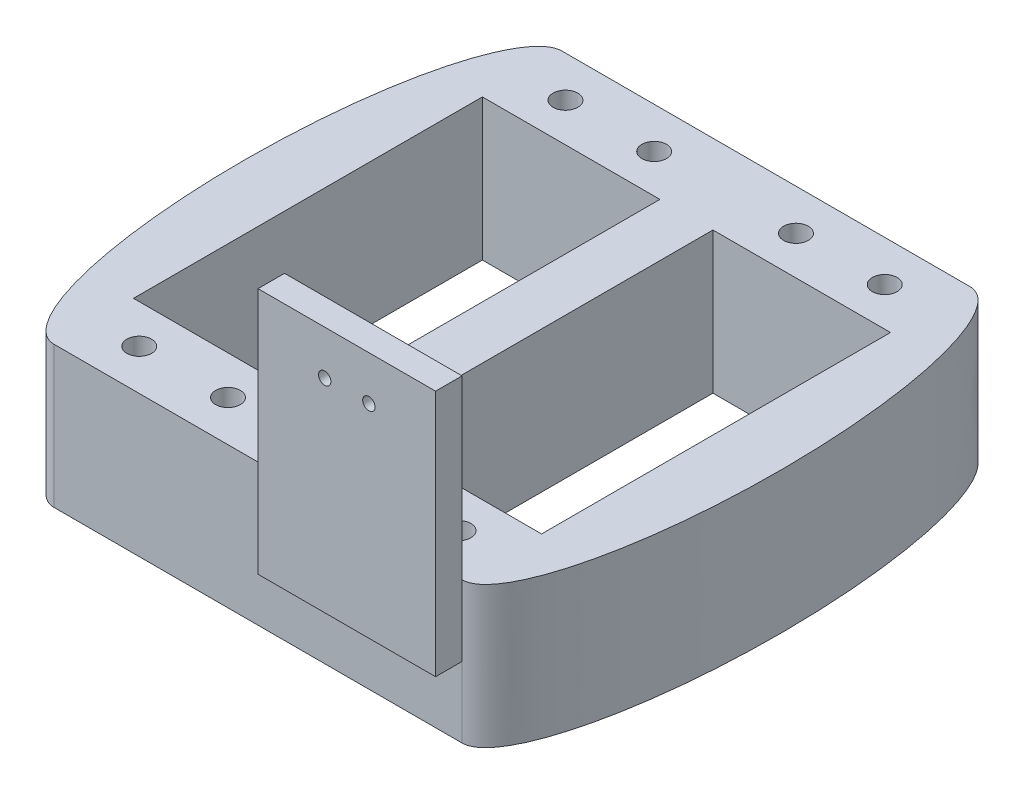
SolidWorks part; units mm, degrees
ref_plane "Front" through (0, 0, 0) normal (0, 0, 1) x (1, 0, 0)
ref_plane "Top" through (0, 0, 0) normal (0, 1, 0) x (1, 0, 0)
ref_plane "Right" through (0, 0, 0) normal (1, 0, 0) x (0, 0, -1)
sketch "Эскиз1" plane through (0, 0, 0) normal (0, 1, 0) x (1, 0, 0)
  line L0 (0, 19.75) -> (0, -19.75) construction
  line L1 (-22.3672, 0) -> (21.2348, 0) construction
  line L2 (0, -19.75) -> (0, -28.75) construction
  line L3 (-10.05, -19.75) -> (10.05, -19.75)
  line L4 (-10.05, -19.75) -> (-10.05, 19.75)
  line L5 (-10.05, 19.75) -> (10.05, 19.75)
  line L6 (10.05, -19.75) -> (10.05, 19.75)
  line L7 (-10.05, -19.75) -> (10.05, 19.75) construction
  line L8 (-10.05, 19.75) -> (10.05, -19.75) construction
  line L9 (10.05, -19.75) -> (-10.05, -19.75)
  line L10 (10.05, -19.75) -> (10.05, -28.75)
  line L11 (10.05, -28.75) -> (-10.05, -28.75)
  line L12 (-10.05, -19.75) -> (-10.05, -28.75)
  line L13 (10.05, 19.75) -> (-10.05, 19.75)
  line L14 (10.05, 19.75) -> (10.05, 28.75)
  line L15 (10.05, 28.75) -> (-10.05, 28.75)
  line L16 (-10.05, 19.75) -> (-10.05, 28.75)
  line L17 (0, 19.75) -> (0, 28.75) construction
  line L18 (10.05, -24.125) -> (5.025, -24.125) construction
  line L19 (5.025, -24.125) -> (-5.025, -24.125) construction
  line L20 (-5.025, -24.125) -> (-10.05, -24.125) construction
  line L21 (-10.05, 24.25) -> (-5.025, 24.125) construction
  line L22 (-5.025, 24.125) -> (5.025, 24.125) construction
  line L23 (5.025, 24.125) -> (10.05, 24.25) construction
  line L24 (-13.05, -28.75) -> (-13.05, 28.75) construction
  line L25 (-31.125, 24.125) -> (-36.15, 24.25) construction
  line L26 (-21.075, 24.125) -> (-31.125, 24.125) construction
  line L27 (-16.05, 24.25) -> (-21.075, 24.125) construction
  line L28 (-21.075, -24.125) -> (-16.05, -24.125) construction
  line L29 (-31.125, -24.125) -> (-21.075, -24.125) construction
  line L30 (-36.15, -24.125) -> (-31.125, -24.125) construction
  line L31 (-26.1, 19.75) -> (-26.1, 28.75) construction
  line L32 (-16.05, 19.75) -> (-36.15, -19.75) construction
  line L33 (-16.05, -19.75) -> (-36.15, 19.75) construction
  line L34 (-26.1, -19.75) -> (-26.1, -28.75) construction
  line L35 (-26.1, 19.75) -> (-26.1, -19.75) construction
  line L36 (-16.05, 19.75) -> (-16.05, 28.75)
  line L37 (-36.15, 28.75) -> (-16.05, 28.75)
  line L38 (-36.15, 19.75) -> (-36.15, 28.75)
  line L39 (-36.15, 19.75) -> (-16.05, 19.75)
  line L40 (-16.05, -19.75) -> (-16.05, -28.75)
  line L41 (-36.15, -28.75) -> (-16.05, -28.75)
  line L42 (-36.15, -19.75) -> (-36.15, -28.75)
  line L43 (-36.15, -19.75) -> (-16.05, -19.75)
  line L44 (-36.15, -19.75) -> (-36.15, 19.75)
  line L45 (-16.05, 19.75) -> (-36.15, 19.75)
  line L46 (-16.05, -19.75) -> (-16.05, 19.75)
  line L47 (-16.05, -19.75) -> (-36.15, -19.75)
  line L48 (-16.05, -28.75) -> (-10.05, -28.75)
  line L49 (-16.05, 28.75) -> (-10.05, 28.75)
  line L50 (-10.05, -28.75) -> (-10.05, -31.75)
  line L51 (-10.05, -31.75) -> (10.05, -31.75)
  line L52 (10.05, -31.75) -> (10.05, -28.75)
  circle A0 centre (5.025, -24.125) radius 1.4
  circle A1 centre (-5.025, -24.125) radius 1.4
  circle A2 centre (-5.025, 24.125) radius 1.4
  circle A3 centre (5.025, 24.125) radius 1.4
  circle A4 centre (-31.125, 24.125) radius 1.4
  circle A5 centre (-21.075, 24.125) radius 1.4
  circle A6 centre (-21.075, -24.125) radius 1.4
  circle A7 centre (-31.125, -24.125) radius 1.4
  ellipse E0 centre (10.05, 0) end of major axis (10.05, 28.75) minor radius 7.2824 (10.05, 28.75) -> (10.05, -28.75) cw
  ellipse E1 centre (-36.15, 0) end of major axis (-36.15, 28.75) minor radius 7.2824 (-36.15, 28.75) -> (-36.15, -28.75) ccw
  point P5 (0, 0)
  point P54 (-26.1, 0)
  point P55 (10.05, 0)
  dimension "D3" = 2.8
  dimension "D1" = 39.5
  dimension "D2" = 20.1
  dimension "D4" = 10.05
  dimension "D5" = 48.25
  dimension "D6" = 9
  dimension "D7" = 3
  dimension "D8" = 3
extrude "Бобышка-Вытянуть2" add sketch "Эскиз1" along normal blind 8 and the other way blind 8 contours L38 E1 L42 L44 | L43 L42 L41 L40 A6 A7 | L49 L36 L46 L40 L48 L12 L4 L16 | L3 L12 L11 L10 A0 A1 | E0 L14 L6 L10 | L16 L5 L14 L15 A2 A3 | L38 L39 L36 L37 A4 A5 region at (-13.05, 0, 0) region at (0, 0, 24.2591) region at (13.1426, 0, 0) region at (0, 0, -24.2591) region at (-26.1, 0, 24.2591) region at (-26.1, 0, -24.2591) region at (-39.241, 0, 0)
extrude "Бобышка-Вытянуть3" add sketch "Эскиз1<4>" along normal blind 28 contours L51 L52 L11 L50 region at (0, 0, 30.25)
sketch "Эскиз1<4>" plane through (0, 0, 0) normal (0, 1, 0) x (1, 0, 0) same geometry as "Эскиз1"
sketch "Эскиз3" plane through (0, 0, 28.75) normal (0, 0, -1) x (-1, 0, 0)
  line L0 (0, 8) -> (0, 28) construction
  line L1 (10.05, 8) -> (-10.05, 8) construction
  line L2 (-10.05, 28) -> (10.05, 28) construction
  line L3 (-6.942, 23) -> (0, 23) construction
  line L6 (-10.05, 8) -> (10.05, 8) construction
  line L7 (0, 23) -> (5.7795, 23) construction
  circle A0 centre (-2.5, 23) radius 0.7
  circle A1 centre (2.5, 23) radius 0.7
  dimension "D2" = 5
  dimension "D1" = 15
extrude "Вырез-Вытянуть1" cut sketch "Эскиз3" against normal blind 28
